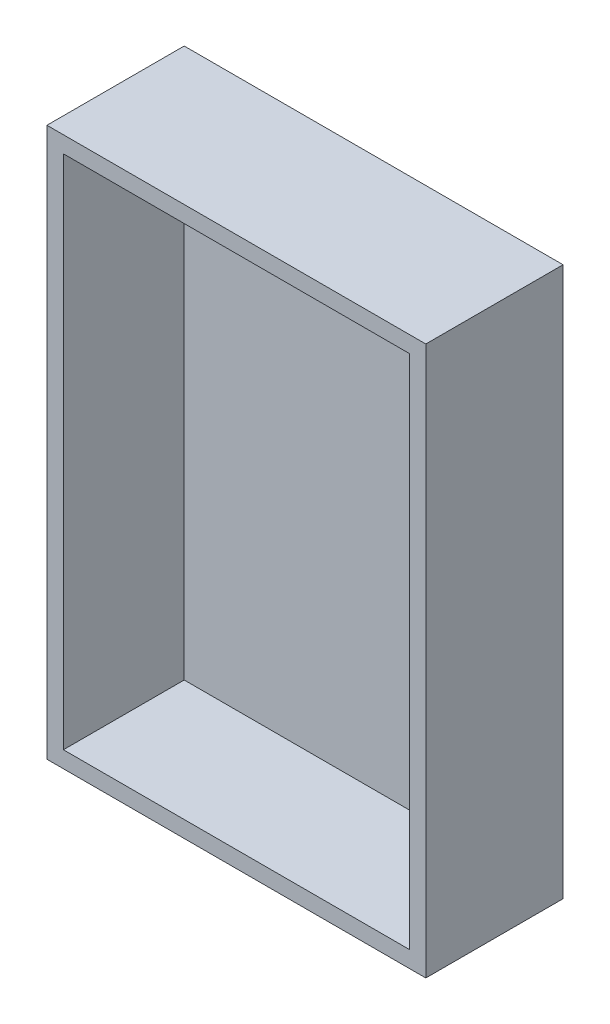
SolidWorks part; units mm, degrees
ref_plane "Ön Düzlem" through (0, 0, 0) normal (0, 0, 1) x (1, 0, 0)
ref_plane "Üst Düzlem" through (0, 0, 0) normal (0, 1, 0) x (1, 0, 0)
ref_plane "Sağ Düzlem" through (0, 0, 0) normal (1, 0, 0) x (0, 0, -1)
sketch "Çizim1" plane through (0, 0, 0) normal (0, 0, 1) x (1, 0, 0)
  line L0 (-34.5, 50) -> (34.5, -50) construction
  line L1 (-34.5, 50) -> (34.5, 50)
  line L2 (-34.5, 50) -> (-34.5, -50)
  line L3 (-34.5, -50) -> (34.5, -50)
  line L4 (34.5, 50) -> (34.5, -50)
  dimension "D1" = 100
  dimension "D2" = 69
extrude "Yükseklik-Ekstrüzyon1" add sketch "Çizim1" along normal blind 3
sketch "Çizim2" plane through (0, 0, 3) normal (0, 0, 1) x (1, 0, 0)
  line L0 (-31.5, 47) -> (-31.5, -47)
  line L1 (-34.5, 50) -> (34.5, 50)
  line L2 (-34.5, 50) -> (-34.5, -50)
  line L3 (-34.5, -50) -> (34.5, -50)
  line L4 (34.5, 50) -> (34.5, -50)
  line L5 (-31.5, -47) -> (31.5, -47)
  line L6 (31.5, 47) -> (31.5, -47)
  line L7 (-31.5, 47) -> (31.5, 47)
  dimension "D1" = 3
extrude "Yükseklik-Ekstrüzyon2" add sketch "Çizim2" along normal blind 22
